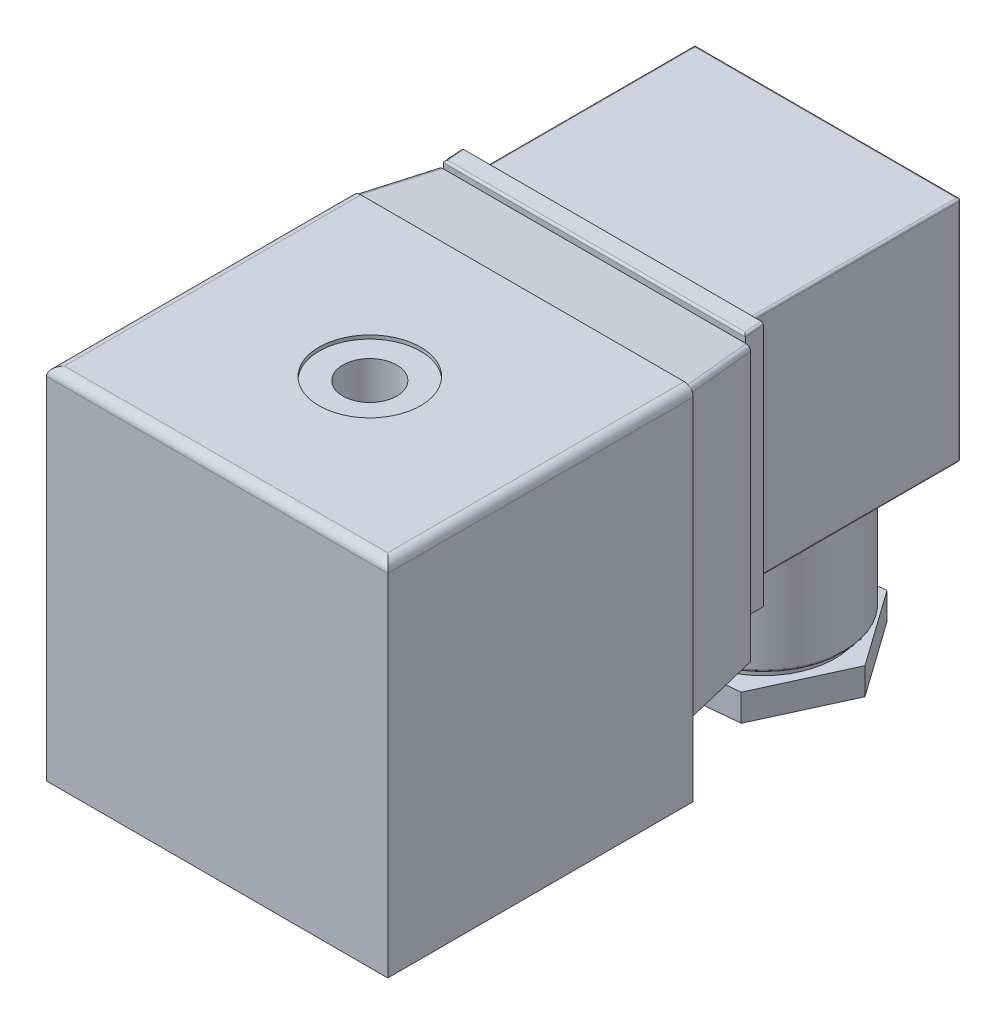
SolidWorks part; units mm, degrees
material "PVC 0.007 Plasticized"
ref_plane "Front Plane" through (0, 0, 0) normal (0, 0, 1) x (1, 0, 0)
ref_plane "Top Plane" through (0, 0, 0) normal (0, 1, 0) x (1, 0, 0)
ref_plane "Right Plane" through (0, 0, 0) normal (1, 0, 0) x (0, 0, -1)
sketch "Sketch2" plane through (0, 0, 0) normal (0, 0, 1) x (1, 0, 0)
  line L1 (0, 0) -> (48.26, 0)
  line L2 (0, 0) -> (0, 50.8)
  line L3 (0, 50.8) -> (48.26, 50.8)
  line L4 (48.26, 0) -> (48.26, 50.8)
  dimension "D1" = 48.26
  dimension "D2" = 50.8
extrude "Boss-Extrude1" add sketch "Sketch2" along normal blind 43.18
fillet "Fillet1" radius 1.27 3 edges at (0, 50.8, 21.59) (48.26, 50.8, 21.59) (24.13, 50.8, 43.18)
sketch "Sketch3" plane through (0, 0, 0) normal (0, 0, -1) x (-1, 0, 0)
  line L0 (-48.26, 0) -> (-48.26, 49.53) construction
  line L1 (-45.466, 50.546) -> (-2.794, 50.546)
  line L2 (-48.006, 48.006) -> (-48.006, 10.16)
  line L3 (-48.006, 10.16) -> (-0.254, 10.16)
  line L4 (-0.254, 48.006) -> (-0.254, 10.16)
  line L5 (0, 49.53) -> (0, 0) construction
  line L6 (-46.99, 50.8) -> (-1.27, 50.8) construction
  line L7 (0, 0) -> (-48.26, 0) construction
  line L8 (-48.006, 48.006) -> (-48.006, 50.546)
  line L9 (-48.006, 50.546) -> (-45.466, 50.546)
  line L10 (-2.794, 50.546) -> (-0.254, 50.546)
  line L11 (-0.254, 50.546) -> (-0.254, 48.006)
  dimension "D1" = 0.254
  dimension "D2" = 0.254
  dimension "D3" = 0.254
  dimension "D5" = 10.16
extrude "Boss-Extrude2" add sketch "Sketch3" along normal blind 10.16
chamfer "Chamfer1" distance 10.16 angle 5 2 edges at (24.13, 50.546, -10.16) (24.13, 10.16, -10.16) tangent propagation no first distance on face at (24.13, 50.546, -3.3867) first distance on face at (24.13, 10.16, -5.08)
sketch "Sketch4" plane through (0, 50.8, 0) normal (0, 1, 0) x (1, 0, 0)
  circle A0 centre (24.13, -21.59) radius 7.1832
extrude "Cut-Extrude1" cut sketch "Sketch4" against normal blind 0.508
chamfer "Chamfer4" distance 10.16 angle 10 2 edges at (48.006, 30.353, -10.16) (0.254, 30.353, -10.16) tangent propagation no first distance on face at (48.006, 34.3408, -4.064) first distance on face at (0.254, 34.3408, -4.064)
sketch "Sketch6" plane through (0, 0, -10.16) normal (0, 0, -1) x (-1, 0, 0)
  line L0 (-45.466, 16.1289) -> (-45.466, 50.9271)
  line L2 (-2.794, 16.1289) -> (-2.794, 50.9271)
  line L4 (-2.794, 50.9271) -> (-45.466, 50.9271)
  line L5 (-45.466, 16.1289) -> (-2.794, 16.1289)
  line L6 (-46.2145, 11.0489) -> (-2.0455, 11.0489) construction
  line L10 (-2.0455, 49.6571) -> (-46.2145, 49.6571) construction
  dimension "D1" = 5.08
  dimension "D4" = 1.27
extrude "Boss-Extrude3" add sketch "Sketch6" along normal blind 2.54
chamfer "Chamfer2" distance 2.54 angle 5 1 edges at (24.13, 50.9271, -10.16) first distance on face at (24.13, 50.9271, -11.43)
fillet "Fillet4" radius 0.3175 3 edges at (45.466, 50.816, -11.43) (2.794, 50.816, -11.43) (24.13, 50.7049, -10.16)
sketch "Sketch8" plane through (0, 0, -12.7) normal (0, 0, -1) x (-1, 0, 0)
  line L0 (-45.466, 50.6084) -> (-45.466, 16.1289) construction
  line L1 (-42.926, 49.6571) -> (-5.334, 49.6571)
  line L2 (-42.926, 49.6571) -> (-42.926, 17.3989)
  line L3 (-42.926, 17.3989) -> (-5.334, 17.3989)
  line L4 (-5.334, 49.6571) -> (-5.334, 17.3989)
  line L5 (-2.794, 16.1289) -> (-2.794, 50.6084) construction
  line L6 (-45.466, 16.1289) -> (-2.794, 16.1289) construction
  line L7 (-3.1115, 50.9271) -> (-45.1485, 50.9271) construction
  dimension "D1" = 2.54
  dimension "D2" = 1.27
  dimension "D3" = 2.54
  dimension "D4" = 1.27
extrude "Boss-Extrude4" add sketch "Sketch8" along normal blind 30.48
fillet "Fillet5" radius 0.3175 3 edges at (5.334, 49.6571, -27.94) (24.13, 49.6571, -43.18) (42.926, 49.6571, -27.94)
fillet "Fillet6" radius 0.3175 4 edges at (5.334, 33.3693, -43.18) (42.926, 33.3693, -43.18) (24.13, 17.3989, -43.18) (42.926, 17.3989, -27.94) tangent propagation no
fillet "Fillet7" radius 0.3175 2 edges at (5.427, 17.4919, -43.087) (5.334, 17.3989, -27.7812)
sketch "Sketch10" plane through (0, 17.3989, 0) normal (0, -1, 0) x (1, 0, 0)
  line L2 (42.6085, -43.18) -> (5.6515, -43.18) construction
  line L3 (5.334, -42.8625) -> (5.334, -12.7) construction
  circle A0 centre (27.686, -30.48) radius 11.43
  dimension "D1" = 12.7
  dimension "D2" = 22.86
  dimension "D3" = 22.352
extrude "Boss-Extrude5" add sketch "Sketch10" along normal blind 19.05
sketch "Sketch11" plane through (0, -1.6511, 0) normal (0, -1, 0) x (1, 0, 0)
  line L0 (27.686, -41.91) -> (27.686, -30.48)
  circle A0 centre (27.686, -30.48) radius 11.43 construction
  circle A1 centre (27.686, -30.48) radius 11.43 construction
  circle A2 centre (27.686, -30.48) radius 10.16
  dimension "D1" = 1.27
extrude "Boss-Extrude6" add sketch "Sketch11" along normal blind 1.27 contours A2 region at (34.667, -1.6511, -37.461)
sketch "Sketch12" plane through (0, -2.9211, 0) normal (0, -1, 0) x (1, 0, 0)
  line L1 (33.1813, -42.4798) -> (40.8258, -31.7209)
  line L2 (40.8258, -31.7209) -> (35.3305, -19.7211)
  line L3 (35.3305, -19.7211) -> (22.1907, -18.4802)
  line L4 (22.1907, -18.4802) -> (14.5462, -29.2391)
  line L5 (14.5462, -29.2391) -> (20.0415, -41.2389)
  line L6 (20.0415, -41.2389) -> (33.1813, -42.4798)
  circle A0 centre (27.686, -30.48) radius 11.43 construction
extrude "Boss-Extrude7" add sketch "Sketch12" along normal blind 3.81
fillet "Fillet8" radius 0.3175 1 edges at (27.686, -1.6511, -41.91)
fillet "Fillet2" radius 0.635 2 edges at (1.1497, 50.1016, -5.08) (47.1103, 50.1016, -5.08)
hole_wizard "3/64 (0.3) Diameter Hole1" positions "Sketch13" profile "Sketch14" hole size "3/64" standard "ANSI Inch" end condition through all
sketch "Sketch13" plane through (0, 50.292, 0) normal (0, 1, 0) x (1, 0, 0)
  point P0 (24.13, -21.59)
sketch "Sketch14" plane through (24.13, 50.292, 21.59) normal (1, 0, 0) x (0, 0, 1)
  line L0 (0, 0) -> (0, 57.0231)
  line L1 (0, 57.0231) -> (3.81, 57.0231)
  line L2 (3.81, 57.0231) -> (3.81, 0)
  line L5 (3.81, 0) -> (0, 0)
  line L11 (0, -6.35) -> (0, 107.95) construction
  dimension "Thru Hole Dia." = 7.62
  dimension "Thru Hole Depth" = 57.0231
